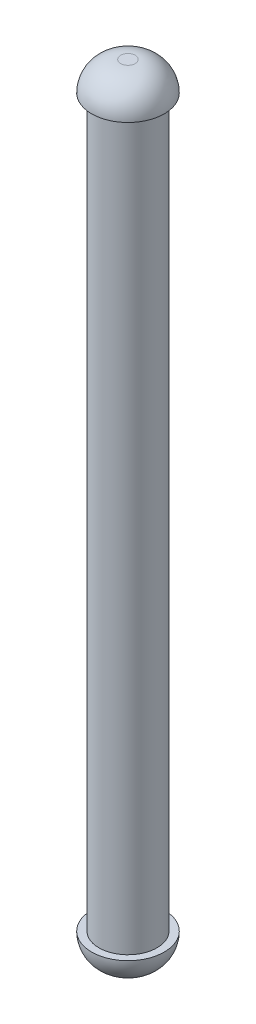
SolidWorks part; units mm, degrees
ref_plane "Front Plane" through (0, 0, 0) normal (0, 0, 1) x (1, 0, 0)
ref_plane "Top Plane" through (0, 0, 0) normal (0, 1, 0) x (1, 0, 0)
ref_plane "Right Plane" through (0, 0, 0) normal (1, 0, 0) x (0, 0, -1)
sketch "Sketch1" plane through (0, 0, 0) normal (0, 1, 0) x (1, 0, 0)
  circle A0 centre (0, 0) radius 1
  dimension "D1" = 2
extrude "Boss-Extrude1" add sketch "Sketch1" along normal blind 25
sketch "Sketch2" plane through (0, 0, 0) normal (0, 1, 0) x (1, 0, 0)
  circle A0 centre (0, 0) radius 1.25
  dimension "D1" = 2.5
extrude "Boss-Extrude2" add sketch "Sketch2" against normal blind 1
fillet "Fillet1" radius 1 1 edges at (0, -1, 1.25)
sketch "Sketch3" plane through (0, 0, 0) normal (0, 1, 0) x (1, 0, 0)
  circle A0 centre (0, 0) radius 1.25
  dimension "D1" = 2.5
extrude "Boss-Extrude5" add sketch "Sketch3" along direction (0, 1, 0) on the side of the normal blind 1 from offset 25
fillet "Fillet2" radius 1 1 edges at (0, 26, 1.25)
